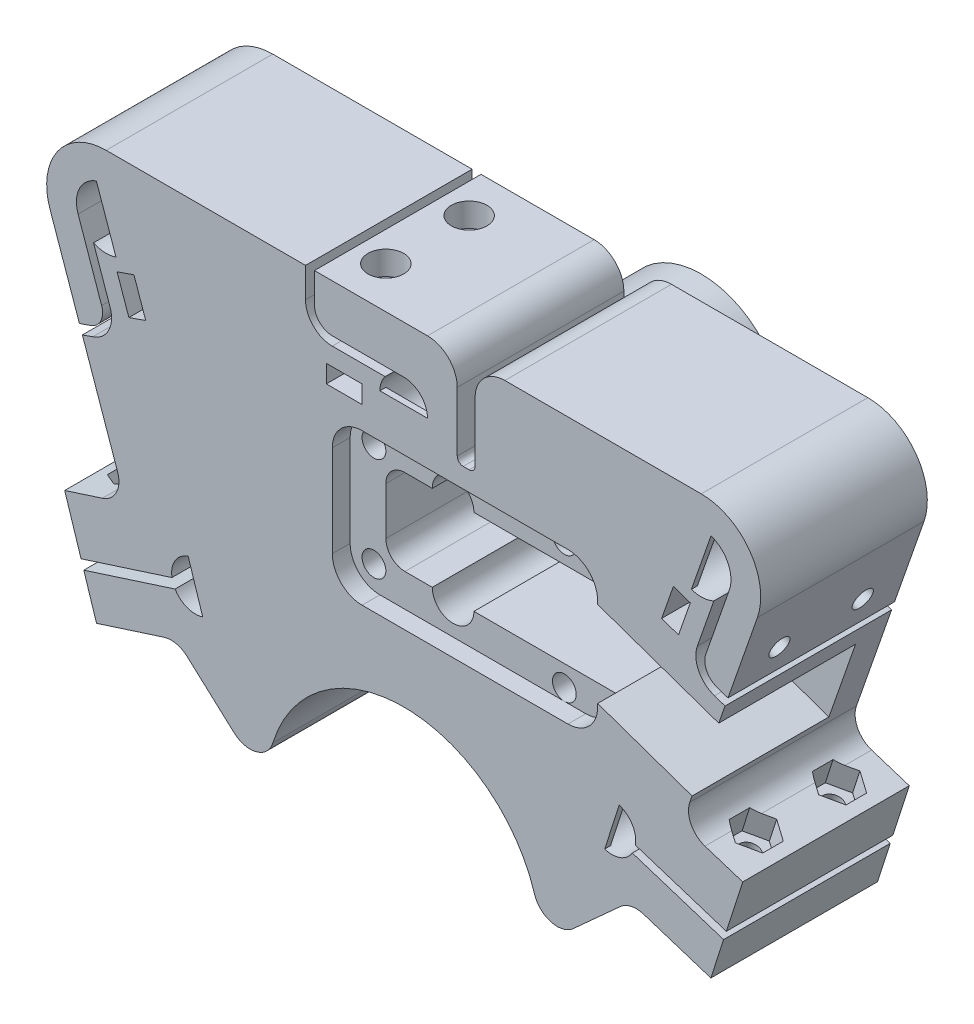
SolidWorks part; units mm, degrees
other "Uwaga1"
sketch "Szkic11" plane through (60, 10, 0) normal (0.4049, 0.0419, -0.9134) x (0.8662, -0.3375, 0.3685)
other "Uwaga2"
sketch "Szkic12" plane through (60, 10, 0) normal (0.4049, 0.0419, -0.9134) x (0.8662, -0.3375, 0.3685)
other "Uwaga3"
sketch "Szkic13"
other "Uwaga4"
sketch "Szkic23" plane through (60, 10, 28) normal (0.2859, 0.0316, 0.9577) x (0.9579, -0.038, -0.2847)
ref_plane "Płaszczyzna przednia" through (0, 0, 0) normal (0, 0, 1) x (1, 0, 0)
ref_plane "Płaszczyzna górna" through (0, 0, 0) normal (0, 1, 0) x (1, 0, 0)
ref_plane "Płaszczyzna prawa" through (0, 0, 0) normal (1, 0, 0) x (0, 0, -1)
sketch "Szkic1" plane through (0, 0, 0) normal (0, 0, 1) x (1, 0, 0)
  line L0 (-50, 10) -> (4, 10)
  line L1 (-59.4412, -3.296) -> (-43.4971, -48.9664)
  line L2 (43.4971, -48.9664) -> (59.4412, -3.296)
  line L3 (-41.0394, -52.6727) -> (-23, -69)
  line L4 (23, -69) -> (41.0394, -52.6727)
  line L5 (38.4257, -48.0651) -> (43.2433, -49.6122)
  line L6 (38.9457, -46.6566) -> (43.7633, -48.2037)
  line L7 (0, -34.7604) -> (35, -46) construction
  line L8 (38.1168, -55.318) -> (51.621, -59.6546)
  line L9 (51.621, -59.6546) -> (53.7613, -52.9898)
  line L10 (53.7613, -52.9898) -> (43.2433, -49.6122)
  line L11 (43.7633, -48.2037) -> (54.2199, -51.5616)
  line L12 (54.2199, -51.5616) -> (56.9717, -42.9926)
  line L13 (56.9717, -42.9926) -> (46.7307, -39.704)
  line L14 (0, -29) -> (0, -114.3862) construction
  line L15 (0, 2) -> (-12, 2)
  line L16 (-3.1225, 0.5) -> (-12, 0.5)
  line L17 (-16.5, 5) -> (-16.5, 10)
  line L18 (-15, 5) -> (-15, 10)
  line L19 (9, 5) -> (9, -5)
  line L20 (10, -6) -> (11, -6)
  line L21 (12, -5) -> (12, 5)
  line L22 (17, 10) -> (50, 10)
  line L23 (-56.9717, -42.9926) -> (-46.7307, -39.704)
  line L24 (-54.2199, -51.5616) -> (-56.9717, -42.9926)
  line L25 (-43.7633, -48.2037) -> (-54.2199, -51.5616)
  line L26 (-38.9457, -46.6566) -> (-43.7633, -48.2037)
  line L27 (-38.4257, -48.0651) -> (-43.2433, -49.6122)
  line L28 (-53.7613, -52.9898) -> (-43.2433, -49.6122)
  line L29 (-51.621, -59.6546) -> (-53.7613, -52.9898)
  line L30 (-38.1168, -55.318) -> (-51.621, -59.6546)
  line L31 (-54.7206, -1.648) -> (-50.7653, -12.9775)
  line L32 (-52.1248, -4.5261) -> (-49.3471, -12.4823)
  line L33 (-52.6089, -16.7986) -> (-54.4971, -17.4578)
  line L34 (-52.2456, -18.2606) -> (-54.0027, -18.874)
  line L35 (54.7206, -1.648) -> (50.7653, -12.9775)
  line L36 (52.1248, -4.5261) -> (49.3471, -12.4823)
  line L37 (52.6089, -16.7986) -> (54.4971, -17.4578)
  line L38 (52.2456, -18.2606) -> (54.0027, -18.874)
  circle A0 centre (-50, 0) radius 5
  circle A1 centre (50, 0) radius 5
  circle A2 centre (-50, 0) radius 10
  circle A3 centre (50, 0) radius 10
  circle A4 centre (0, -2) radius 4
  circle A5 centre (0, -29) radius 15.5 construction
  circle A6 centre (0, -22) radius 4
  circle A13 centre (-35, -46) radius 4
  circle A14 centre (35, -46) radius 4
  circle A15 centre (-35, -46) radius 9
  circle A16 centre (35, -46) radius 9
  arc A17 (23, -69) -> (-23, -69) centre (0, -69) ccw
  arc A19 (-12, 2) -> (-15, 5) centre (-12, 5) cw
  arc A20 (-12, 0.5) -> (-16.5, 5) centre (-12, 5) cw
  arc A21 (9, 5) -> (4, 10) centre (4, 5) ccw
  arc A22 (12, 5) -> (17, 10) centre (17, 5) cw
  arc A23 (11, -6) -> (12, -5) centre (11, -5) ccw
  arc A24 (9, -5) -> (10, -6) centre (10, -5) ccw
  arc A25 (-50.7653, -12.9775) -> (-52.6089, -16.7986) centre (-53.5977, -13.9663) cw
  arc A26 (-49.3471, -12.4823) -> (-52.2456, -18.2606) centre (-53.5977, -13.9663) cw
  arc A27 (49.3471, -12.4823) -> (52.2456, -18.2606) centre (53.5977, -13.9663) ccw
  arc A28 (50.7653, -12.9775) -> (52.6089, -16.7986) centre (53.5977, -13.9663) ccw
  point P32 (0, -29)
  point P78 (10.1421, 10)
  point P84 (10.1421, -2)
  point P87 (7.1421, -2)
  point P103 (-49.7765, -15.8098)
  dimension "D1" = 10
  dimension "D6" = 8
  dimension "D8" = 31
  dimension "D9" = 8
  dimension "D14" = 70
  dimension "D18" = 46
  dimension "D27" = 3
  dimension "D28" = 4.5
  dimension "D31" = 5
  dimension "D32" = 5
  dimension "D33" = 1
  dimension "D38" = 3
  dimension "D39" = 12.7604
  dimension "D2" = 100
  dimension "D3" = 50
  dimension "D7" = 39
  dimension "D10" = 7
  dimension "D11" = 12
  dimension "D15" = 35
  dimension "D16" = 46
  dimension "D19" = 40
  dimension "D20" = 1.5
  dimension "D21" = 7
  dimension "D22" = 20
  dimension "D23" = 9
  dimension "D24" = 1.5
  dimension "D25" = 1.5
  dimension "D26" = 15
  dimension "D29" = 3
  dimension "D30" = 16
  dimension "D34" = 9
  dimension "D35" = 15
  dimension "D36" = 1.5021
  dimension "D37" = 1.5
  dimension "D4" = 5
  dimension "D5" = 5
  dimension "D17" = 5
extrude "Dodanie-wyciągnięcie1" add sketch "Szkic1" along normal blind 28 contours A2 A0 | A17 L4 A16 L2 A3 L0 A2 L1 A15 L3 A6 A4 | A3 A1 | A16 A14 | A15 A13 | A16 L4 L8 L9 L10 | L12 L13 L2 L11 | A15 L28 L29 L30 L3 | L25 L1 L23 L24 | A25 L31 A2 L1 L33 | L35 A28 L37 L2 A3 region at (-33.25, 8.6619, 0) region at (-43.1289, 6.8711, 0) region at (-54.1165, -12.2056, 0) region at (-50.4165, -45.6303, 0) region at (-36.0734, -37.3207, 0) region at (-46.741, -54.5771, 0) region at (56.8711, 6.8711, 0) region at (46.741, -54.5771, 0) region at (54.1165, -12.2056, 0) region at (27.0061, -42.4532, 0) region at (50.4165, -45.6303, 0)
fillet "Zaokrąglenie1" radius 4 6 edges at (-46.7307, -39.704, 14) (-38.1168, -55.318, 14) (-23, -69, 14) (23, -69, 14) (38.1168, -55.318, 14) (46.7307, -39.704, 14)
sketch "Szkic2" plane through (12.5403, -39.0504, 0) normal (0.3058, -0.9521, 0) x (0.9521, 0.3058, 0)
  line L0 (-55.5122, 28) -> (-67.3885, 28) construction
  line L1 (-67.3885, 28) -> (-67.3885, 0) construction
  circle A0 centre (-62.3885, 21) radius 1.7
  circle A1 centre (-62.3885, 7) radius 1.7
  dimension "D1" = 14
  dimension "D4" = 3.4
  dimension "D2" = 7
  dimension "D3" = 5
extrude "Wytnij-wyciągnięcie1" cut sketch "Szkic2" against normal through all
sketch "Szkic3" plane through (12.5403, -39.0504, 0) normal (0.3058, -0.9521, 0) x (0.9521, 0.3058, 0)
  circle A0 centre (-62.3885, 21) radius 3
  circle A1 centre (-62.3885, 7) radius 3
  dimension "D1" = 6
extrude "Wytnij-wyciągnięcie2" cut sketch "Szkic3" against normal blind 3
sketch "Szkic4" plane through (7.1896, -22.3885, 0) normal (-0.3058, 0.9521, 0) x (0.9521, 0.3058, 0)
  line L1 (-62.3885, -24.4641) -> (-59.3885, -22.7321)
  line L2 (-59.3885, -22.7321) -> (-59.3885, -19.2679)
  line L3 (-59.3885, -19.2679) -> (-62.3885, -17.5359)
  line L4 (-62.3885, -17.5359) -> (-65.3885, -19.2679)
  line L5 (-65.3885, -19.2679) -> (-65.3885, -22.7321)
  line L6 (-65.3885, -22.7321) -> (-62.3885, -24.4641)
  line L7 (-62.3885, -10.4641) -> (-59.3885, -8.7321)
  line L8 (-59.3885, -8.7321) -> (-59.3885, -5.2679)
  line L9 (-59.3885, -5.2679) -> (-62.3885, -3.5359)
  line L10 (-62.3885, -3.5359) -> (-65.3885, -5.2679)
  line L11 (-65.3885, -5.2679) -> (-65.3885, -8.7321)
  line L12 (-65.3885, -8.7321) -> (-62.3885, -10.4641)
  circle A0 centre (-62.3885, -21) radius 3 construction
  circle A1 centre (-62.3885, -7) radius 3 construction
  dimension "D1" = 6
extrude "Wytnij-wyciągnięcie3" cut sketch "Szkic4" against normal blind 4 and the other way blind 4
sketch "Szkic5" plane through (-54.0092, -18.8553, 0) normal (-0.9441, -0.3296, 0) x (0, 0, 1)
  line L0 (28, 16.4802) -> (28, 1.4802) construction
  line L1 (28, 1.4802) -> (0, 1.4802) construction
  circle A0 centre (21, 6.4802) radius 1.7
  circle A1 centre (7, 6.4802) radius 1.7
  dimension "D1" = 14
  dimension "D2" = 3.4
  dimension "D3" = 7
  dimension "D4" = 5
extrude "Wytnij-wyciągnięcie4" cut sketch "Szkic5" against normal blind 10
sketch "Szkic6" plane through (-54.0092, -18.8553, 0) normal (-0.9441, -0.3296, 0) x (0, 0, 1)
  line L0 (22.7321, 9.4802) -> (28, 9.4802)
  line L1 (24.4641, 6.4802) -> (22.7321, 9.4802)
  line L2 (22.7321, 9.4802) -> (19.2679, 9.4802)
  line L3 (19.2679, 9.4802) -> (17.5359, 6.4802)
  line L4 (17.5359, 6.4802) -> (19.2679, 3.4802)
  line L5 (19.2679, 3.4802) -> (22.7321, 3.4802)
  line L6 (22.7321, 3.4802) -> (24.4641, 6.4802)
  line L7 (10.4641, 6.4802) -> (8.7321, 9.4802)
  line L8 (8.7321, 9.4802) -> (5.2679, 9.4802)
  line L9 (5.2679, 9.4802) -> (3.5359, 6.4802)
  line L10 (3.5359, 6.4802) -> (5.2679, 3.4802)
  line L11 (5.2679, 3.4802) -> (8.7321, 3.4802)
  line L12 (8.7321, 3.4802) -> (10.4641, 6.4802)
  line L13 (28, 16.4802) -> (28, 1.4802) construction
  line L14 (28, 9.4802) -> (28, 3.4802)
  line L15 (28, 3.4802) -> (22.7321, 3.4802)
  line L16 (5.2679, 9.4802) -> (0, 9.4802)
  line L17 (0, 16.4802) -> (0, 1.4802) construction
  line L18 (0, 9.4802) -> (0, 3.4802)
  line L19 (0, 3.4802) -> (5.2679, 3.4802)
  circle A0 centre (21, 6.4802) radius 3 construction
  circle A1 centre (7, 6.4802) radius 3 construction
  circle M2 centre (21, 6.4802) radius 1.7
  circle M3 centre (7, 6.4802) radius 1.7
  line M4 (0, 16.4802) -> (0, 1.4802)
  line M6 (28, 1.4802) -> (28, 16.4802)
  dimension "D1" = 6
extrude "Wytnij-wyciągnięcie5" cut sketch "Szkic6" against normal blind 3 from offset 9.5 contours L5 L6 L1 L2 L3 L4 M2 | L15 L0 L1 L6 M6 | L19 L10 L9 L16 M4 | L11 L12 L7 L8 L9 L10 M3 | M2 | M3 region at (-56.1452, -12.7372, 25.7706) region at (-56.6245, -11.3643, 23.5187) region at (-55.6658, -14.1101, 9.5187) region at (-56.1452, -12.7372, 2.2294) region at (-56.1452, -12.7372, 21) region at (-56.1452, -12.7372, 7) offset against normal yes
mirror "Lustro1" about plane through (0, 0, 0) normal (1, 0, 0) of "Wytnij-wyciągnięcie5", "Wytnij-wyciągnięcie4", "Wytnij-wyciągnięcie2", "Wytnij-wyciągnięcie1", "Wytnij-wyciągnięcie3"
sketch "Szkic7" plane through (0, 10, 0) normal (0, 1, 0) x (1, 0, 0)
  line L0 (-15, 0) -> (4, 0) construction
  line L1 (-15, -28) -> (-15, 0) construction
  circle A0 centre (-10, -21) radius 1.7
  circle A1 centre (-10, -7) radius 1.7
  dimension "D1" = 3.4
  dimension "D2" = 14
  dimension "D3" = 7
  dimension "D4" = 5
extrude "Wytnij-wyciągnięcie6" cut sketch "Szkic7" against normal blind 14
sketch "Szkic8" plane through (0, 10, 0) normal (0, 1, 0) x (1, 0, 0)
  line L0 (-7, -22.7321) -> (-7, -28)
  line L1 (-10, -24.4641) -> (-7, -22.7321)
  line L2 (-7, -22.7321) -> (-7, -19.2679)
  line L3 (-7, -19.2679) -> (-10, -17.5359)
  line L4 (-10, -17.5359) -> (-13, -19.2679)
  line L5 (-13, -19.2679) -> (-13, -22.7321)
  line L6 (-13, -22.7321) -> (-10, -24.4641)
  line L7 (-10, -10.4641) -> (-7, -8.7321)
  line L8 (-7, -8.7321) -> (-7, -5.2679)
  line L9 (-7, -5.2679) -> (-10, -3.5359)
  line L10 (-10, -3.5359) -> (-13, -5.2679)
  line L11 (-13, -5.2679) -> (-13, -8.7321)
  line L12 (-13, -8.7321) -> (-10, -10.4641)
  line L13 (-15, -28) -> (4, -28) construction
  line L14 (-7, -28) -> (-13, -28)
  line L15 (-13, -28) -> (-13, -22.7321)
  line L16 (-7, -5.2679) -> (-7, 0)
  line L17 (-15, 0) -> (4, 0) construction
  line L18 (-7, 0) -> (-13, 0)
  line L19 (-13, 0) -> (-13, -5.2679)
  circle A0 centre (-10, -21) radius 3 construction
  circle A1 centre (-10, -7) radius 3 construction
  circle M1 centre (-10, -21) radius 1.7
  circle M2 centre (-10, -7) radius 1.7
  line M3 (4, 0) -> (-15, 0)
  line M5 (-15, -28) -> (4, -28)
  dimension "D1" = 6
extrude "Wytnij-wyciągnięcie7" cut sketch "Szkic8" against normal blind 3 from offset 12.5 contours L5 L6 L1 L2 L3 L4 M1 | M1 | L15 L0 L1 L6 M5 | M2 | L11 L12 L7 L8 L9 L10 M2 | L19 L10 L9 L16 M3 region at (-10, 10, 25.7706) region at (-8.5458, 10, 23.5187) region at (-11.4542, 10, 9.5187) region at (-10, 10, 2.2294) region at (-10, 10, 21) region at (-10, 10, 7) offset against normal yes
sketch "Szkic9" plane through (0, 0, 28) normal (0, 0, 1) x (1, 0, 0)
  line L0 (-36.223, -42.1916) -> (-33.777, -49.8084)
  line L1 (36.223, -42.1916) -> (33.777, -49.8084)
  line L2 (-51.648, 4.7206) -> (-48.352, -4.7206)
  line L3 (51.648, 4.7206) -> (48.352, -4.7206)
  line L4 (-4, -2) -> (4, -2)
  line L36 (-36.4063, -56.8662) -> (-28.4915, -64.0297)
  line L37 (28.4915, -64.0297) -> (36.4063, -56.8662)
  line L38 (40.3135, -56.0234) -> (51.621, -59.6546)
  line L39 (51.621, -59.6546) -> (53.7613, -52.9898)
  line L40 (53.7613, -52.9898) -> (38.4257, -48.0651)
  line L41 (38.9457, -46.6566) -> (54.2199, -51.5616)
  line L42 (54.2199, -51.5616) -> (56.9717, -42.9926)
  line L43 (56.9717, -42.9926) -> (50.6362, -40.9581)
  line L44 (48.0827, -35.8313) -> (54.0027, -18.874)
  line L45 (54.0027, -18.874) -> (52.2456, -18.2606)
  line L46 (49.3471, -12.4823) -> (52.1248, -4.5261)
  line L47 (54.7206, -1.648) -> (50.7653, -12.9775)
  line L48 (52.6089, -16.7986) -> (54.4971, -17.4578)
  line L49 (54.4971, -17.4578) -> (59.4412, -3.296)
  line L50 (50, 10) -> (17, 10)
  line L51 (12, 5) -> (12, -5)
  line L52 (11, -6) -> (10, -6)
  line L53 (9, -5) -> (9, 5)
  line L54 (4, 10) -> (-15, 10)
  line L55 (-15, 10) -> (-15, 5)
  line L56 (-12, 2) -> (0, 2)
  line L57 (-3.1225, 0.5) -> (-12, 0.5)
  line L58 (-16.5, 5) -> (-16.5, 10)
  line L59 (-16.5, 10) -> (-50, 10)
  line L60 (-59.4412, -3.296) -> (-54.4971, -17.4578)
  line L61 (-54.4971, -17.4578) -> (-52.6089, -16.7986)
  line L62 (-50.7653, -12.9775) -> (-54.7206, -1.648)
  line L63 (-52.1248, -4.5261) -> (-49.3471, -12.4823)
  line L64 (-52.2456, -18.2606) -> (-54.0027, -18.874)
  line L65 (-54.0027, -18.874) -> (-48.0827, -35.8313)
  line L66 (-50.6362, -40.9581) -> (-56.9717, -42.9926)
  line L67 (-56.9717, -42.9926) -> (-54.2199, -51.5616)
  line L68 (-54.2199, -51.5616) -> (-38.9457, -46.6566)
  line L69 (-38.4257, -48.0651) -> (-53.7613, -52.9898)
  line L70 (-53.7613, -52.9898) -> (-51.621, -59.6546)
  line L71 (-51.621, -59.6546) -> (-40.3135, -56.0234)
  line L72 (-36.4063, -56.8662) -> (-28.4915, -64.0297)
  line L73 (28.4915, -64.0297) -> (36.4063, -56.8662)
  line L74 (40.3135, -56.0234) -> (51.621, -59.6546)
  line L75 (51.621, -59.6546) -> (53.7613, -52.9898)
  line L76 (53.7613, -52.9898) -> (38.4257, -48.0651)
  line L77 (38.9457, -46.6566) -> (54.2199, -51.5616)
  line L78 (54.2199, -51.5616) -> (56.9717, -42.9926)
  line L79 (56.9717, -42.9926) -> (50.6362, -40.9581)
  line L80 (48.0827, -35.8313) -> (54.0027, -18.874)
  line L81 (54.0027, -18.874) -> (52.2456, -18.2606)
  line L82 (49.3471, -12.4823) -> (52.1248, -4.5261)
  line L83 (54.7206, -1.648) -> (50.7653, -12.9775)
  line L84 (52.6089, -16.7986) -> (54.4971, -17.4578)
  line L85 (54.4971, -17.4578) -> (59.4412, -3.296)
  line L86 (50, 10) -> (17, 10)
  line L87 (12, 5) -> (12, -5)
  line L88 (11, -6) -> (10, -6)
  line L89 (9, -5) -> (9, 5)
  line L90 (4, 10) -> (-15, 10)
  line L91 (-15, 10) -> (-15, 5)
  line L92 (-12, 2) -> (0, 2)
  line L93 (-3.1225, 0.5) -> (-12, 0.5)
  line L94 (-16.5, 5) -> (-16.5, 10)
  line L95 (-16.5, 10) -> (-50, 10)
  line L96 (-59.4412, -3.296) -> (-54.4971, -17.4578)
  line L97 (-54.4971, -17.4578) -> (-52.6089, -16.7986)
  line L98 (-50.7653, -12.9775) -> (-54.7206, -1.648)
  line L99 (-52.1248, -4.5261) -> (-49.3471, -12.4823)
  line L100 (-52.2456, -18.2606) -> (-54.0027, -18.874)
  line L101 (-54.0027, -18.874) -> (-48.0827, -35.8313)
  line L102 (-50.6362, -40.9581) -> (-56.9717, -42.9926)
  line L103 (-56.9717, -42.9926) -> (-54.2199, -51.5616)
  line L104 (-54.2199, -51.5616) -> (-38.9457, -46.6566)
  line L105 (-38.4257, -48.0651) -> (-53.7613, -52.9898)
  line L106 (-53.7613, -52.9898) -> (-51.621, -59.6546)
  line L107 (-51.621, -59.6546) -> (-40.3135, -56.0234)
  arc A24 (-28.4915, -64.0297) -> (-21.984, -62.2397) centre (-25.8074, -61.064) ccw
  arc A25 (21.984, -62.2397) -> (-21.984, -62.2397) centre (0, -69) ccw
  arc A26 (21.984, -62.2397) -> (28.4915, -64.0297) centre (25.8074, -61.064) ccw
  arc A27 (40.3135, -56.0234) -> (36.4063, -56.8662) centre (39.0904, -59.8318) ccw
  arc A28 (38.9457, -46.6566) -> (38.4257, -48.0651) centre (35, -46) ccw
  arc A29 (48.0827, -35.8313) -> (50.6362, -40.9581) centre (51.8592, -37.1497) ccw
  arc A30 (49.3471, -12.4823) -> (52.2456, -18.2606) centre (53.5977, -13.9663) ccw
  arc A31 (54.7206, -1.648) -> (52.1248, -4.5261) centre (50, 0) ccw
  arc A32 (50.7653, -12.9775) -> (52.6089, -16.7986) centre (53.5977, -13.9663) ccw
  arc A33 (59.4412, -3.296) -> (50, 10) centre (50, 0) ccw
  arc A34 (17, 10) -> (12, 5) centre (17, 5) ccw
  arc A35 (11, -6) -> (12, -5) centre (11, -5) ccw
  arc A36 (9, -5) -> (10, -6) centre (10, -5) ccw
  arc A37 (9, 5) -> (4, 10) centre (4, 5) ccw
  arc A38 (-15, 5) -> (-12, 2) centre (-12, 5) ccw
  arc A39 (-3.1225, 0.5) -> (0, 2) centre (0, -2) ccw
  arc A40 (-16.5, 5) -> (-12, 0.5) centre (-12, 5) ccw
  arc A41 (-50, 10) -> (-59.4412, -3.296) centre (-50, 0) ccw
  arc A42 (-52.6089, -16.7986) -> (-50.7653, -12.9775) centre (-53.5977, -13.9663) ccw
  arc A43 (-52.1248, -4.5261) -> (-54.7206, -1.648) centre (-50, 0) ccw
  arc A44 (-52.2456, -18.2606) -> (-49.3471, -12.4823) centre (-53.5977, -13.9663) ccw
  arc A45 (-50.6362, -40.9581) -> (-48.0827, -35.8313) centre (-51.8592, -37.1497) ccw
  arc A46 (-38.4257, -48.0651) -> (-38.9457, -46.6566) centre (-35, -46) ccw
  arc A47 (-36.4063, -56.8662) -> (-40.3135, -56.0234) centre (-39.0904, -59.8318) ccw
  arc A48 (-28.4915, -64.0297) -> (-21.984, -62.2397) centre (-25.8074, -61.064) ccw
  arc A49 (21.984, -62.2397) -> (-21.984, -62.2397) centre (0, -69) ccw
  arc A50 (21.984, -62.2397) -> (28.4915, -64.0297) centre (25.8074, -61.064) ccw
  arc A51 (40.3135, -56.0234) -> (36.4063, -56.8662) centre (39.0904, -59.8318) ccw
  arc A52 (38.9457, -46.6566) -> (38.4257, -48.0651) centre (35, -46) ccw
  arc A53 (48.0827, -35.8313) -> (50.6362, -40.9581) centre (51.8592, -37.1497) ccw
  arc A54 (49.3471, -12.4823) -> (52.2456, -18.2606) centre (53.5977, -13.9663) ccw
  arc A55 (54.7206, -1.648) -> (52.1248, -4.5261) centre (50, 0) ccw
  arc A56 (50.7653, -12.9775) -> (52.6089, -16.7986) centre (53.5977, -13.9663) ccw
  arc A57 (59.4412, -3.296) -> (50, 10) centre (50, 0) ccw
  arc A58 (17, 10) -> (12, 5) centre (17, 5) ccw
  arc A59 (11, -6) -> (12, -5) centre (11, -5) ccw
  arc A60 (9, -5) -> (10, -6) centre (10, -5) ccw
  arc A61 (9, 5) -> (4, 10) centre (4, 5) ccw
  arc A62 (-15, 5) -> (-12, 2) centre (-12, 5) ccw
  arc A63 (-3.1225, 0.5) -> (0, 2) centre (0, -2) ccw
  arc A64 (-16.5, 5) -> (-12, 0.5) centre (-12, 5) ccw
  arc A65 (-50, 10) -> (-59.4412, -3.296) centre (-50, 0) ccw
  arc A66 (-52.6089, -16.7986) -> (-50.7653, -12.9775) centre (-53.5977, -13.9663) ccw
  arc A67 (-52.1248, -4.5261) -> (-54.7206, -1.648) centre (-50, 0) ccw
  arc A68 (-52.2456, -18.2606) -> (-49.3471, -12.4823) centre (-53.5977, -13.9663) ccw
  arc A69 (-50.6362, -40.9581) -> (-48.0827, -35.8313) centre (-51.8592, -37.1497) ccw
  arc A70 (-38.4257, -48.0651) -> (-38.9457, -46.6566) centre (-35, -46) ccw
  arc A71 (-36.4063, -56.8662) -> (-40.3135, -56.0234) centre (-39.0904, -59.8318) ccw
  dimension "D1" = 0
extrude "Dodanie-wyciągnięcie2" add sketch "Szkic9" against normal blind 1 contours L2 A67 | L4 A63 | L3 A55 | L1 A52 | L0 A70 region at (-33.3836, -45.4809, 28) region at (-47.9965, 0.6994, 28) region at (33.3836, -45.4809, 28) region at (0, -3.6977, 28) region at (47.9965, 0.6994, 28)
sketch "Szkic14" plane through (0, 10, 0) normal (0, 1, 0) x (1, 0, 0)
  circle A0 centre (-10, -7) radius 3
  circle A1 centre (-10, -21) radius 3
  dimension "D1" = 6
extrude "Wytnij-wyciągnięcie9" cut sketch "Szkic14" against normal blind 4
sketch "Szkic15" plane through (0, 0, 28) normal (0, 0, 1) x (1, 0, 0)
  line L0 (-6, -26) -> (-6, -18)
  line L1 (-2.8, -29.2) -> (1.8, -29.2)
  line L2 (-2.8, -14.8) -> (1.8, -14.8)
  line L3 (8.8, -29.2) -> (22.6, -29.2)
  line L4 (22.6, -29.2) -> (22.6, -14.8)
  line L5 (22.6, -14.8) -> (8.8, -14.8)
  line L6 (22.6, -14.8) -> (32.6, -14.8)
  line L7 (32.6, -14.8) -> (32.6, -29.2)
  line L8 (32.6, -29.2) -> (22.6, -29.2)
  line L9 (32.6, -14.8) -> (52.9453, -21.9028)
  line L10 (48.0827, -35.8313) -> (54.0027, -18.874) construction
  line L11 (32.6, -29.2) -> (48.4643, -34.7384)
  line L12 (52.9453, -21.9028) -> (48.4643, -34.7384)
  circle A1 centre (0, -22) radius 4
  arc A2 (-6, -18) -> (-2.8, -14.8) centre (-2.8, -18) cw
  arc A3 (-6, -26) -> (-2.8, -29.2) centre (-2.8, -26) ccw
  arc A6 (1.8, -29.2) -> (8.8, -29.2) centre (5.3, -29.2) ccw
  circle A7 centre (0, -22) radius 4 construction
  circle A8 centre (0, -22) radius 4
  arc A9 (8.8, -14.8) -> (1.8, -14.8) centre (5.3, -14.8) ccw
  dimension "D2" = 3.2
  dimension "D5" = 7
  dimension "D7" = 28.6
  dimension "D8" = 10
  dimension "D1" = 6
  dimension "D3" = 14.4
  dimension "D4" = 7.2
  dimension "D6" = 11.3
extrude "Wytnij-wyciągnięcie10" cut sketch "Szkic15" against normal blind 23 contours L5 A9 L2 A2 L0 A3 L1 A6 L3 L4 A1 | L8 L7 L6 L4 | L12 L9 L7 L11 region at (9.2135, -22, 28) region at (27.6, -22, 28) region at (41.6986, -24.8794, 28)
sketch "Szkic16" plane through (0, 0, 28) normal (0, 0, 1) x (1, 0, 0)
  line L0 (-6, -26) -> (-6, -18) construction
  line L1 (-7, -9.3) -> (27.6, -9.3)
  line L2 (-12, -14.3) -> (-12, -29.7)
  line L3 (-7, -34.7) -> (27.6, -34.7)
  line L4 (32.6, -14.3) -> (32.6, -29.7)
  line L5 (32.6, -14.8) -> (8.8, -14.8) construction
  line L7 (8.8, -29.2) -> (32.6, -29.2) construction
  arc A0 (27.6, -9.3) -> (32.6, -14.3) centre (27.6, -14.3) cw
  arc A1 (27.6, -34.7) -> (32.6, -29.7) centre (27.6, -29.7) ccw
  arc A2 (-12, -29.7) -> (-7, -34.7) centre (-7, -29.7) ccw
  arc A3 (-7, -9.3) -> (-12, -14.3) centre (-7, -14.3) ccw
  dimension "D2" = 5
  dimension "D1" = 5.5
  dimension "D3" = 6
  dimension "D4" = 5.5
  dimension "D5" = 44.6
extrude "Wytnij-wyciągnięcie11" cut sketch "Szkic16" against normal blind 3
sketch "Szkic17" plane through (0, 0, 25) normal (0, 0, 1) x (1, 0, 0)
  line L0 (-12, -14.3) -> (-12, -29.7) construction
  line L1 (27.6, -9.3) -> (-7, -9.3) construction
  line L2 (-7, -34.7) -> (27.6, -34.7) construction
  circle A0 centre (-8, -13.3) radius 2
  circle A1 centre (-8, -30.7) radius 2
  circle A2 centre (24, -32.7) radius 2
  circle A3 centre (24, -11.3) radius 2
  dimension "D1" = 4
  dimension "D2" = 4
  dimension "D3" = 4
  dimension "D4" = 4
  dimension "D5" = 2
  dimension "D6" = 2
  dimension "D7" = 32
extrude "Wytnij-wyciągnięcie12" cut sketch "Szkic17" against normal blind 6
sketch "Szkic18" plane through (0, 0, 5) normal (0, 0, 1) x (1, 0, 0)
  circle A0 centre (5.3, -14.8) radius 2
  circle A1 centre (5.3, -29.2) radius 2
  dimension "D1" = 4
extrude "Wytnij-wyciągnięcie13" cut sketch "Szkic18" against normal blind 4
sketch "Szkic19" plane through (0, 0, 5) normal (0, 0, 1) x (1, 0, 0)
  line L1 (8.8, -18) -> (21.8, -18)
  line L2 (8.8, -18) -> (8.8, -26)
  line L3 (8.8, -26) -> (21.8, -26)
  line L4 (21.8, -18) -> (21.8, -26)
  circle A0 centre (0, -22) radius 4 construction
  circle A1 centre (0, -22) radius 4
  point P8 (8.8, -22)
  dimension "D1" = 8
  dimension "D2" = 13
  dimension "D3" = 8.8
extrude "Wytnij-wyciągnięcie14" cut sketch "Szkic19" against normal blind 4
sketch "Szkic20" plane through (0, 0, 0) normal (0, 0, -1) x (-1, 0, 0)
  circle A0 centre (0, -22) radius 4 construction
  circle A1 centre (0, -22) radius 4
  circle A2 centre (0, -22) radius 14
  dimension "D1" = 28
extrude "Dodanie-wyciągnięcie3" add sketch "Szkic20" along normal blind 22
sketch "Szkic21" plane through (0, 0, -22) normal (0, 0, -1) x (-1, 0, 0)
  circle A0 centre (0, -22) radius 4 construction
  circle A1 centre (0, -22) radius 4
  circle A2 centre (0, -22) radius 14 construction
  circle A3 centre (0, -22) radius 14
  circle A4 centre (0, -22) radius 11.05
  circle M2 centre (0, -22) radius 4
  dimension "D1" = 22.1
extrude "Wytnij-wyciągnięcie15" cut sketch "Szkic21" against normal blind 7 contours A4 M2 region at (10.7375, -22, -22)
sketch "Szkic22" plane through (0, 0, -15) normal (0, 0, -1) x (-1, 0, 0)
  circle A0 centre (0, -22) radius 8
  circle A1 centre (0, -22) radius 4 construction
  circle A2 centre (0, -22) radius 4
  dimension "D1" = 16
extrude "Wytnij-wyciągnięcie16" cut sketch "Szkic22" against normal blind 15
chamfer "Sfazowanie1" distance 2 angle 45 1 edges at (14, -22, 0)
chamfer "Sfazowanie2" distance 5 angle 45 1 edges at (0, -46, 0) tangent propagation no
chamfer "Sfazowanie3" distance 0.5 distance2 12 1 edges at (-8, -22, -15) first distance on face at (-8, -22, -15)
